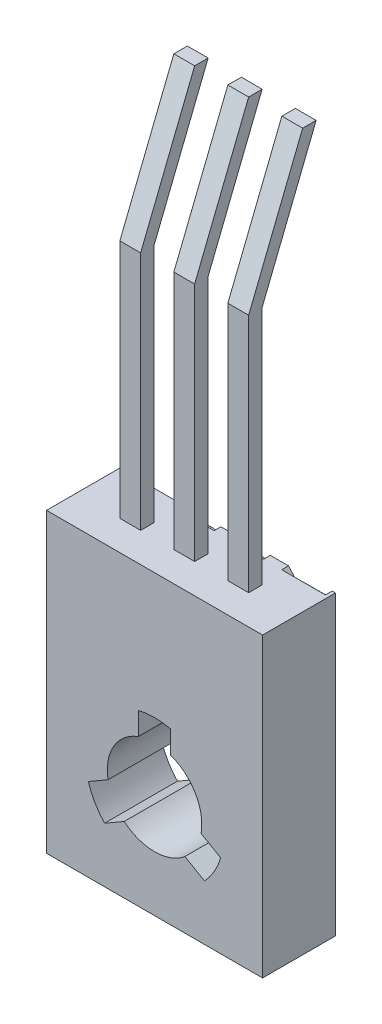
SolidWorks part; units mm, degrees
ref_plane "Front Plane" through (0, 0, 0) normal (0, 0, 1) x (1, 0, 0)
ref_plane "Top Plane" through (0, 0, 0) normal (0, 1, 0) x (1, 0, 0)
ref_plane "Right Plane" through (0, 0, 0) normal (1, 0, 0) x (0, 0, -1)
sketch "Sketch1" plane through (0, 0, 0) normal (0, 0, 1) x (1, 0, 0)
  line L1 (-4, 5.5) -> (4, 5.5)
  line L2 (-4, 5.5) -> (-4, -5.5)
  line L3 (-4, -5.5) -> (4, -5.5)
  line L4 (4, 5.5) -> (4, -5.5)
  line L5 (-4, 5.5) -> (4, -5.5) construction
  line L6 (-4, -5.5) -> (4, 5.5) construction
  circle A0 centre (0, -1.7) radius 2.555
  point P0 (0, 0)
  dimension "D3" = 5.11
  dimension "D1" = 11
  dimension "D2" = 8
  dimension "D4" = 3.8
extrude "Boss-Extrude1" add sketch "Sketch1" along normal mid plane 2.7
sketch "Sketch2" plane through (0, 5.5, 0) normal (0, 1, 0) x (1, 0, 0)
  line L0 (0, 0.8819) -> (0, -0.7814) construction
  line L1 (-0.385, 0.25) -> (0.385, 0.25)
  line L2 (-0.385, 0.25) -> (-0.385, -0.25)
  line L3 (-0.385, -0.25) -> (0.385, -0.25)
  line L4 (0.385, 0.25) -> (0.385, -0.25)
  line L5 (-0.385, 0.25) -> (0.385, -0.25) construction
  line L6 (-0.385, -0.25) -> (0.385, 0.25) construction
  line L7 (-2.385, 0.25) -> (-1.615, 0.25)
  line L8 (-2.385, 0.25) -> (-2.385, -0.25)
  line L9 (-2.385, -0.25) -> (-1.615, -0.25)
  line L10 (-1.615, 0.25) -> (-1.615, -0.25)
  line L11 (-2.385, 0.25) -> (-1.615, -0.25) construction
  line L12 (-2.385, -0.25) -> (-1.615, 0.25) construction
  line L13 (2.385, -0.25) -> (1.615, -0.25)
  line L14 (1.615, 0.25) -> (1.615, -0.25)
  line L15 (2.385, 0.25) -> (1.615, 0.25)
  line L16 (2.385, 0.25) -> (2.385, -0.25)
  point P0 (0, 0)
  point P7 (-2, 0)
  dimension "D1" = 0.5
  dimension "D2" = 0.77
  dimension "D3" = 0.77
  dimension "D4" = 0.5
  dimension "D5" = 2
extrude "Boss-Extrude2" add sketch "Sketch2" along normal blind 8.9
sketch "Sketch4" plane through (0, 0, 1.35) normal (0, 0, 1) x (1, 0, 0)
  line L0 (0, 0.8936) -> (0, -1.7) construction
  line L3 (-0.6, 0.8232) -> (-0.6, -0.0561)
  line L4 (0.6, 0.8232) -> (0.6, -0.0561)
  line L5 (2.4852, -2.442) -> (1.7237, -2.0023)
  line L6 (1.8852, -3.4812) -> (1.1237, -3.0416)
  line L7 (-1.8852, -3.4812) -> (-1.1237, -3.0416)
  line L8 (-2.4852, -2.442) -> (-1.7237, -2.0023)
  arc A0 (-1.1237, -3.0416) -> (1.1237, -3.0416) centre (0, -1.7) ccw
  arc A1 (-1.8852, -3.4812) -> (1.8852, -3.4812) centre (0, -1.7) ccw
  arc A2 (-0.6, -0.0561) -> (-1.7237, -2.0023) centre (0, -1.7) ccw
  arc A3 (-0.6, 0.8232) -> (-2.4852, -2.442) centre (0, -1.7) ccw
  arc A4 (1.7237, -2.0023) -> (0.6, -0.0561) centre (0, -1.7) ccw
  arc A5 (2.4852, -2.442) -> (0.6, 0.8232) centre (0, -1.7) ccw
  point P22 (0, -1.7)
  dimension "D1" = 3.5
  dimension "D2" = 0.6
  dimension "D3" = 3
extrude "Boss-Extrude3" add sketch "Sketch4" against normal up to surface (2.7 mm away) up to face at (0, 0, -1.35)
sketch "Sketch5" plane through (0, 0, -1.35) normal (0, 0, -1) x (-1, 0, 0)
  text T0 "D882" font "Century Gothic" height in points 9
extrude "Cut-Extrude1" cut sketch "Sketch5" against normal blind 0.25
sketch "Sketch7" plane through (0, 0, 0) normal (1, 0, 0) x (0, 0, -1)
  line L0 (0, 14.4) -> (1.9999, 19.4)
  line L1 (-0.25, 14.4) -> (0.25, 14.4) construction
  line L3 (0, 14.4) -> (0, 19.4) construction
  point P4 (0, 0)
  point P5 (0, 0)
  dimension "D1" = 21.8
  dimension "D2" = 5
  dimension "D3" = 1.9999
sketch "Sketch8" plane through (0, 14.4, 0) normal (0, 1, 0) x (1, 0, 0)
  line L0 (2.385, -0.25) -> (2.385, 0.25) construction
  line L1 (2.385, 0.25) -> (1.615, 0.25) construction
  line L2 (1.615, 0.25) -> (1.615, -0.25) construction
  line L3 (1.615, -0.25) -> (2.385, -0.25) construction
  line L4 (0.385, -0.25) -> (0.385, 0.25) construction
  line L5 (0.385, 0.25) -> (-0.385, 0.25) construction
  line L6 (-0.385, 0.25) -> (-0.385, -0.25) construction
  line L7 (-0.385, -0.25) -> (0.385, -0.25) construction
  line L8 (-1.615, -0.25) -> (-1.615, 0.25) construction
  line L9 (-1.615, 0.25) -> (-2.385, 0.25) construction
  line L10 (-2.385, 0.25) -> (-2.385, -0.25) construction
  line L11 (-2.385, -0.25) -> (-1.615, -0.25) construction
  line L12 (2.385, -0.25) -> (2.385, 0.25)
  line L13 (2.385, 0.25) -> (1.615, 0.25)
  line L14 (1.615, 0.25) -> (1.615, -0.25)
  line L15 (1.615, -0.25) -> (2.385, -0.25)
  line L16 (0.385, -0.25) -> (0.385, 0.25)
  line L17 (0.385, 0.25) -> (-0.385, 0.25)
  line L18 (-0.385, 0.25) -> (-0.385, -0.25)
  line L19 (-0.385, -0.25) -> (0.385, -0.25)
  line L20 (-1.615, -0.25) -> (-1.615, 0.25)
  line L21 (-1.615, 0.25) -> (-2.385, 0.25)
  line L22 (-2.385, 0.25) -> (-2.385, -0.25)
  line L23 (-2.385, -0.25) -> (-1.615, -0.25)
sweep "Sweep1" add profiles "Sketch8" path "Sketch7"
